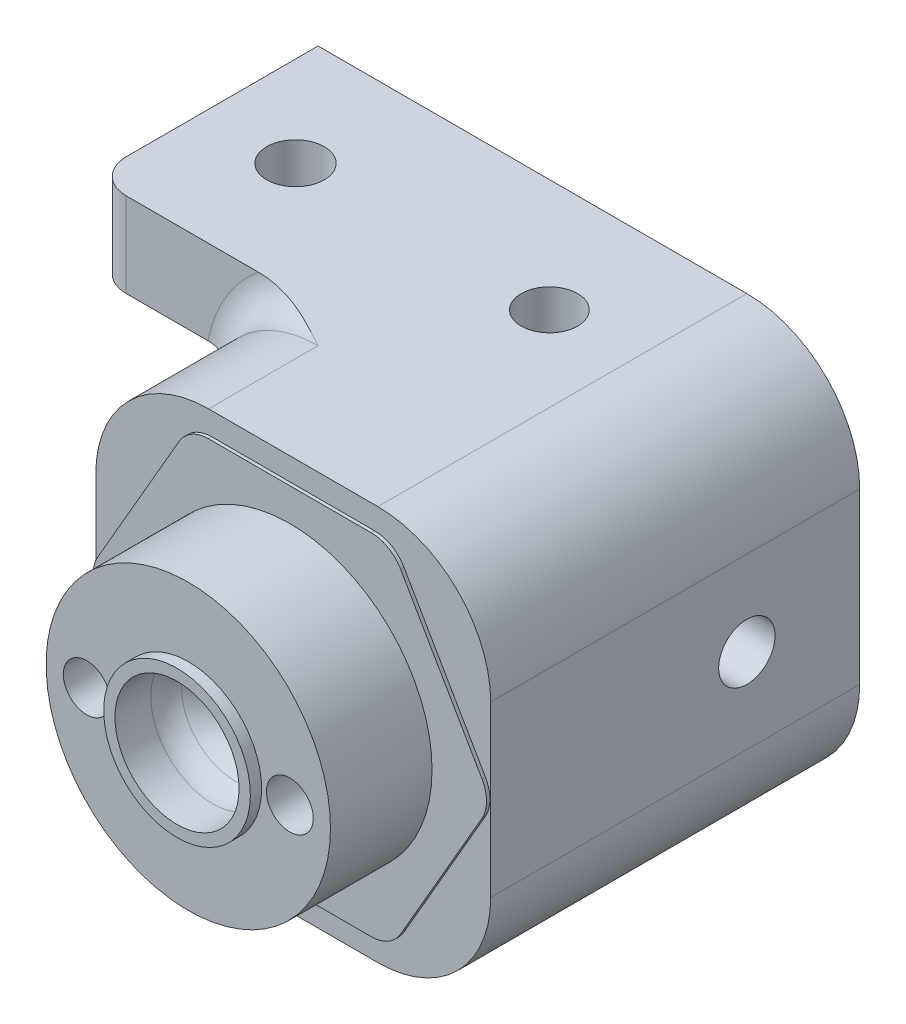
SolidWorks part; units mm, degrees
ref_plane "前视基准面" through (0, 0, 0) normal (0, 0, 1) x (1, 0, 0)
ref_plane "上视基准面" through (0, 0, 0) normal (0, 1, 0) x (1, 0, 0)
ref_plane "右视基准面" through (0, 0, 0) normal (1, 0, 0) x (0, 0, -1)
sketch "草图1" plane through (0, 0, 0) normal (0, 0, 1) x (1, 0, 0)
  circle A0 centre (0, 0) radius 12.6
  dimension "D1" = 25.2
extrude "凸台-拉伸1" add sketch "草图1" along normal blind 9
sketch "草图2" plane through (0, 0, 0) normal (0, 0, -1) x (-1, 0, 0)
  circle A0 centre (0, 0) radius 15
  dimension "D1" = 30
extrude "凸台-拉伸2" add sketch "草图2" along normal blind 5
sketch "草图3" plane through (0, 0, 9) normal (0, 0, 1) x (1, 0, 0)
  circle A0 centre (0, 0) radius 5.5
  dimension "D1" = 11
extrude "切除-拉伸1" cut sketch "草图3" against normal blind 5
sketch "草图4" plane through (0, 0, 9) normal (0, 0, 1) x (1, 0, 0)
  circle A0 centre (-9, 0) radius 2.075
  circle A1 centre (9, 0) radius 2.075
  dimension "D1" = 4.15
  dimension "D2" = 9
  dimension "D3" = 9
extrude "切除-拉伸2" cut sketch "草图4" against normal blind 29
sketch "草图5" plane through (0, 0, 4) normal (0, 0, 1) x (1, 0, 0)
  circle A0 centre (0, 0) radius 3.5
  dimension "D1" = 7
extrude "切除-拉伸3" cut sketch "草图5" against normal blind 31
fillet "圆角1" radius 3 1 edges at (5.5, 0, 4)
fillet "圆角2" radius 5 1 edges at (3.5, 0, 4)
sketch "草图6" plane through (0, 0, 9) normal (0, 0, 1) x (1, 0, 0)
  circle A0 centre (0, 0) radius 5.5
  dimension "D1" = 11
extrude "拉伸-薄壁1" add sketch "草图6" along normal blind 1 thin thin type one direction wall 1
sketch "草图7" plane through (0, 0, -5) normal (0, 0, -1) x (-1, 0, 0)
  line L1 (-8.9489, 15.5) -> (-17.8979, 0)
  line L2 (-17.8979, 0) -> (-8.9489, -15.5)
  line L3 (-8.9489, -15.5) -> (8.9489, -15.5)
  line L4 (8.9489, -15.5) -> (17.8979, 0)
  line L5 (17.8979, 0) -> (8.9489, 15.5)
  line L6 (8.9489, 15.5) -> (-8.9489, 15.5)
  circle A0 centre (0, 0) radius 15.5 construction
  circle A1 centre (0, 0) radius 15
  circle A2 centre (0, 0) radius 15
  dimension "D2" = 31
  dimension "D1" = 0
extrude "凸台-拉伸3" add sketch "草图7" against normal up to surface (5 mm away) up to face at (12.6, 0, 0)
fillet "圆角3" radius 3 6 edges at (17.8979, 0, -2.5) (8.9489, 15.5, -2.5) (-8.9489, 15.5, -2.5) (-17.8979, 0, -2.5) (-8.9489, -15.5, -2.5) (8.9489, -15.5, -2.5)
sketch "草图8" plane through (0, 0, -5) normal (0, 0, -1) x (-1, 0, 0)
  line L6 (-9.815, 14) -> (-17.0318, 1.5)
  line L7 (-17.0318, -1.5) -> (-9.815, -14)
  line L8 (-7.2169, -15.5) -> (7.2169, -15.5)
  line L9 (9.815, -14) -> (17.0318, -1.5)
  line L10 (17.0318, 1.5) -> (9.815, 14)
  line L11 (7.2169, 15.5) -> (-7.2169, 15.5)
  line L12 (-9.815, 14) -> (-17.0318, 1.5)
  line L13 (-17.0318, -1.5) -> (-9.815, -14)
  line L14 (-7.2169, -15.5) -> (7.2169, -15.5)
  line L15 (9.815, -14) -> (17.0318, -1.5)
  line L16 (17.0318, 1.5) -> (9.815, 14)
  line L17 (7.2169, 15.5) -> (-7.2169, 15.5)
  circle A0 centre (0, 0) radius 3.5 construction
  circle A1 centre (0, 0) radius 3.5
  circle A2 centre (-9, 0) radius 4
  circle A3 centre (9, 0) radius 4
  arc A6 (-17.0318, 1.5) -> (-17.0318, -1.5) centre (-14.4338, 0) ccw
  arc A7 (-9.815, -14) -> (-7.2169, -15.5) centre (-7.2169, -12.5) ccw
  arc A8 (7.2169, -15.5) -> (9.815, -14) centre (7.2169, -12.5) ccw
  arc A9 (17.0318, -1.5) -> (17.0318, 1.5) centre (14.4338, 0) ccw
  arc A10 (9.815, 14) -> (7.2169, 15.5) centre (7.2169, 12.5) ccw
  arc A11 (-7.2169, 15.5) -> (-9.815, 14) centre (-7.2169, 12.5) ccw
  arc A12 (-17.0318, 1.5) -> (-17.0318, -1.5) centre (-14.4338, 0) ccw
  arc A13 (-9.815, -14) -> (-7.2169, -15.5) centre (-7.2169, -12.5) ccw
  arc A14 (7.2169, -15.5) -> (9.815, -14) centre (7.2169, -12.5) ccw
  arc A15 (17.0318, -1.5) -> (17.0318, 1.5) centre (14.4338, 0) ccw
  arc A16 (9.815, 14) -> (7.2169, 15.5) centre (7.2169, 12.5) ccw
  arc A17 (-7.2169, 15.5) -> (-9.815, 14) centre (-7.2169, 12.5) ccw
  dimension "D2" = 8
  dimension "D3" = 8
  dimension "D1" = 0
extrude "凸台-拉伸4" add sketch "草图8" along normal blind 8
sketch "草图9" plane through (0, 0, -13) normal (0, 0, -1) x (-1, 0, 0)
  line L1 (-10, 10) -> (10, 10)
  line L2 (-10, 10) -> (-10, -10)
  line L3 (-10, -10) -> (10, -10)
  line L4 (10, 10) -> (10, -10)
  line L5 (-10, 10) -> (10, -10) construction
  line L6 (-10, -10) -> (10, 10) construction
  line L7 (17.5, -17.5) -> (-17.5, -17.5)
  line L8 (17.5, -17.5) -> (17.5, 17.5)
  line L9 (17.5, 17.5) -> (-17.5, 17.5)
  line L10 (-17.5, -17.5) -> (-17.5, 17.5)
  line L11 (17.5, -17.5) -> (-17.5, 17.5) construction
  line L12 (17.5, 17.5) -> (-17.5, -17.5) construction
  point P0 (0, 0)
  point P6 (0, 0)
  dimension "D1" = 20
  dimension "D2" = 20
  dimension "D3" = 35
  dimension "D4" = 35
extrude "凸台-拉伸5" add sketch "草图9" along normal blind 20
sketch "草图10" plane through (0, 0, -13) normal (0, 0, 1) x (1, 0, 0)
  line L4 (17.5, -17.5) -> (17.5, 17.5)
  line L5 (17.5, 17.5) -> (-17.5, 17.5)
  line L6 (-17.5, 17.5) -> (-17.5, -17.5)
  line L7 (-17.5, -17.5) -> (17.5, -17.5)
  line L8 (17.5, -17.5) -> (17.5, 17.5)
  line L9 (17.5, 17.5) -> (-17.5, 17.5)
  line L10 (-17.5, 17.5) -> (-17.5, -17.5)
  line L11 (-17.5, -17.5) -> (17.5, -17.5)
  line L14 (7.2169, 15.5) -> (-7.2169, 15.5)
  line L15 (17.0318, 1.5) -> (9.815, 14)
  line L16 (9.815, -14) -> (17.0318, -1.5)
  line L17 (-7.2169, -15.5) -> (7.2169, -15.5)
  line L18 (-17.0318, -1.5) -> (-9.815, -14)
  line L19 (-9.815, 14) -> (-17.0318, 1.5)
  line L20 (7.2169, 15.5) -> (-7.2169, 15.5)
  line L21 (17.0318, 1.5) -> (9.815, 14)
  line L22 (9.815, -14) -> (17.0318, -1.5)
  line L23 (-7.2169, -15.5) -> (7.2169, -15.5)
  line L24 (-17.0318, -1.5) -> (-9.815, -14)
  line L25 (-9.815, 14) -> (-17.0318, 1.5)
  arc A6 (9.815, 14) -> (7.2169, 15.5) centre (7.2169, 12.5) ccw
  arc A7 (17.0318, -1.5) -> (17.0318, 1.5) centre (14.4338, 0) ccw
  arc A8 (7.2169, -15.5) -> (9.815, -14) centre (7.2169, -12.5) ccw
  arc A9 (-9.815, -14) -> (-7.2169, -15.5) centre (-7.2169, -12.5) ccw
  arc A10 (-17.0318, 1.5) -> (-17.0318, -1.5) centre (-14.4338, 0) ccw
  arc A11 (-7.2169, 15.5) -> (-9.815, 14) centre (-7.2169, 12.5) ccw
  arc A12 (9.815, 14) -> (7.2169, 15.5) centre (7.2169, 12.5) ccw
  arc A13 (17.0318, -1.5) -> (17.0318, 1.5) centre (14.4338, 0) ccw
  arc A14 (7.2169, -15.5) -> (9.815, -14) centre (7.2169, -12.5) ccw
  arc A15 (-9.815, -14) -> (-7.2169, -15.5) centre (-7.2169, -12.5) ccw
  arc A16 (-17.0318, 1.5) -> (-17.0318, -1.5) centre (-14.4338, 0) ccw
  arc A17 (-7.2169, 15.5) -> (-9.815, 14) centre (-7.2169, 12.5) ccw
  dimension "D1" = 0
  dimension "D2" = 0
extrude "凸台-拉伸6" add sketch "草图10" along normal blind 8.5
fillet "圆角4" radius 10 4 edges at (-17.5, 17.5, -18.75) (-17.5, -17.5, -18.75) (17.5, -17.5, -18.75) (17.5, 17.5, -18.75)
sketch "草图11" plane through (-17.5, 0, 0) normal (-1, 0, 0) x (0, 0, 1)
  line L0 (-33, -7.5) -> (-33, 7.5) construction
  circle A0 centre (-23, 0) radius 2.5
  dimension "D1" = 5
  dimension "D2" = 10
extrude "切除-拉伸4" cut sketch "草图11" against normal blind 15
pattern_circular "阵列(圆周)1" count 4 over 360 about axis through (0, 0, -27) along (0, 0, 1) of "切除-拉伸4"
sketch "草图12" plane through (0, 0, -5) normal (0, 0, -1) x (-1, 0, 0)
  circle A1 centre (9, 0) radius 4
  circle A2 centre (9, 0) radius 4
  circle A3 centre (-9, 0) radius 4
  circle A4 centre (-9, 0) radius 4
  dimension "D1" = 0
  dimension "D2" = 0
extrude "切除-拉伸5" cut sketch "草图12" along normal blind 83
sketch "草图13" plane through (0, 0, -13) normal (0, 0, -1) x (-1, 0, 0)
  line L0 (0, 3.5) -> (0, 10)
  line L1 (10, 10) -> (-10, 10) construction
  line L2 (0, 0) -> (0, 3.5)
  circle A0 centre (0, 0) radius 3.5 construction
extrude "切除-拉伸-薄壁1" [suppressed] cut sketch "草图13" against normal blind 4 thin thin type mid plane wall 4
fillet "圆角5" [suppressed] radius 4
fillet "圆角6" [suppressed] radius 4
fillet "圆角7" [suppressed] radius 3
sketch "草图14" plane through (0, 0, -13) normal (0, 0, -1) x (-1, 0, 0)
  line L0 (-10, -10) -> (10, -10) construction
  line L1 (10, 10) -> (33.2128, 10)
  line L2 (10, 10) -> (10, -10)
  line L3 (10, -10) -> (33.2128, -10)
  line L4 (33.2128, 10) -> (33.2128, -10)
extrude "切除-拉伸6" cut sketch "草图14" along normal blind 41
sketch "草图15" plane through (0, 0, -4.5) normal (0, 0, 1) x (1, 0, 0)
  line L4 (7.5, 17.5) -> (-7.5, 17.5)
  line L5 (-17.5, 7.5) -> (-17.5, -7.5)
  line L6 (-7.5, -17.5) -> (7.5, -17.5)
  line L7 (17.5, -7.5) -> (17.5, 7.5)
  line L8 (7.5, 17.5) -> (-7.5, 17.5)
  line L9 (-17.5, 7.5) -> (-17.5, -7.5)
  line L10 (-7.5, -17.5) -> (7.5, -17.5)
  line L11 (17.5, -7.5) -> (17.5, 7.5)
  line L14 (9.815, -14) -> (17.0318, -1.5)
  line L15 (17.0318, 1.5) -> (9.815, 14)
  line L16 (7.2169, 15.5) -> (-7.2169, 15.5)
  line L17 (-9.815, 14) -> (-17.0318, 1.5)
  line L18 (-17.0318, -1.5) -> (-9.815, -14)
  line L19 (-7.2169, -15.5) -> (7.2169, -15.5)
  line L20 (9.815, -14) -> (17.0318, -1.5)
  line L21 (17.0318, 1.5) -> (9.815, 14)
  line L22 (7.2169, 15.5) -> (-7.2169, 15.5)
  line L23 (-9.815, 14) -> (-17.0318, 1.5)
  line L24 (-17.0318, -1.5) -> (-9.815, -14)
  line L25 (-7.2169, -15.5) -> (7.2169, -15.5)
  arc A4 (-7.5, 17.5) -> (-17.5, 7.5) centre (-7.5, 7.5) ccw
  arc A5 (-17.5, -7.5) -> (-7.5, -17.5) centre (-7.5, -7.5) ccw
  arc A6 (7.5, -17.5) -> (17.5, -7.5) centre (7.5, -7.5) ccw
  arc A7 (17.5, 7.5) -> (7.5, 17.5) centre (7.5, 7.5) ccw
  arc A8 (-7.5, 17.5) -> (-17.5, 7.5) centre (-7.5, 7.5) ccw
  arc A9 (-17.5, -7.5) -> (-7.5, -17.5) centre (-7.5, -7.5) ccw
  arc A10 (7.5, -17.5) -> (17.5, -7.5) centre (7.5, -7.5) ccw
  arc A11 (17.5, 7.5) -> (7.5, 17.5) centre (7.5, 7.5) ccw
  arc A14 (17.0318, -1.5) -> (17.0318, 1.5) centre (14.4338, 0) ccw
  arc A15 (9.815, 14) -> (7.2169, 15.5) centre (7.2169, 12.5) ccw
  arc A16 (-7.2169, 15.5) -> (-9.815, 14) centre (-7.2169, 12.5) ccw
  arc A17 (-17.0318, 1.5) -> (-17.0318, -1.5) centre (-14.4338, 0) ccw
  arc A18 (-9.815, -14) -> (-7.2169, -15.5) centre (-7.2169, -12.5) ccw
  arc A19 (7.2169, -15.5) -> (9.815, -14) centre (7.2169, -12.5) ccw
  arc A20 (17.0318, -1.5) -> (17.0318, 1.5) centre (14.4338, 0) ccw
  arc A21 (9.815, 14) -> (7.2169, 15.5) centre (7.2169, 12.5) ccw
  arc A22 (-7.2169, 15.5) -> (-9.815, 14) centre (-7.2169, 12.5) ccw
  arc A23 (-17.0318, 1.5) -> (-17.0318, -1.5) centre (-14.4338, 0) ccw
  arc A24 (-9.815, -14) -> (-7.2169, -15.5) centre (-7.2169, -12.5) ccw
  arc A25 (7.2169, -15.5) -> (9.815, -14) centre (7.2169, -12.5) ccw
  dimension "D1" = 0
  dimension "D2" = 0
extrude "凸台-拉伸7" add sketch "草图15" along normal blind 1.3
sketch "草图16" plane through (0, 0, -13) normal (0, 0, -1) x (-1, 0, 0)
  line L1 (0, 3.5) -> (-9.9868, 3.5)
  line L2 (0, 3.5) -> (0, -3.5)
  line L3 (0, -3.5) -> (-9.9868, -3.5)
  line L4 (-9.9868, 3.5) -> (-9.9868, -3.5)
  circle A0 centre (0, 0) radius 3.5 construction
  dimension "D1" = 7
extrude "切除-拉伸7" cut sketch "草图16" against normal blind 3
sketch "草图18" plane through (0, 0, -13) normal (0, 0, -1) x (-1, 0, 0)
  line L0 (17.1825, 10) -> (-10, 10) construction
  line L1 (7.5, 17.5) -> (30.5, 17.5)
  line L2 (7.5, 17.5) -> (7.5, 10)
  line L3 (7.5, 10) -> (30.5, 10)
  line L4 (30.5, 17.5) -> (30.5, 10)
  dimension "D1" = 7.5
  dimension "D2" = 23
extrude "凸台-拉伸8" add sketch "草图18" along normal blind 20
sketch "草图19" plane through (0, 17.5, 0) normal (0, 1, 0) x (1, 0, 0)
  line L0 (-30.5, 33) -> (7.5, 33) construction
  line L1 (-30.5, 33) -> (-30.5, 13) construction
  circle A0 centre (-22.5, 23) radius 2.55
  dimension "D1" = 5.1
  dimension "D2" = 10
  dimension "D3" = 8
extrude "切除-拉伸8" cut sketch "草图19" against normal blind 20
mirror "镜向1" about plane through (0, 0, 0) normal (0, 1, 0) of "切除-拉伸8", "凸台-拉伸8"
fillet "圆角8" radius 3 2 edges at (-13.6237, 15.4057, -13) (-13.6237, -15.4057, -13)
fillet "圆角9" radius 3 2 edges at (-30.5, 13.75, -13) (-30.5, -13.75, -13)
sketch "草图20" plane through (0, 0, -3.2) normal (0, 0, 1) x (1, 0, 0)
  line L4 (7.5, 17.5) -> (-7.5, 17.5)
  line L5 (-17.5, 7.5) -> (-17.5, -7.5)
  line L6 (-7.5, -17.5) -> (7.5, -17.5)
  line L7 (17.5, -7.5) -> (17.5, 7.5)
  line L8 (7.5, 17.5) -> (-7.5, 17.5)
  line L9 (-17.5, 7.5) -> (-17.5, -7.5)
  line L10 (-7.5, -17.5) -> (7.5, -17.5)
  line L11 (17.5, -7.5) -> (17.5, 7.5)
  line L14 (9.815, -14) -> (17.0318, -1.5)
  line L15 (17.0318, 1.5) -> (9.815, 14)
  line L16 (7.2169, 15.5) -> (-7.2169, 15.5)
  line L17 (-9.815, 14) -> (-17.0318, 1.5)
  line L18 (-17.0318, -1.5) -> (-9.815, -14)
  line L19 (-7.2169, -15.5) -> (7.2169, -15.5)
  line L20 (9.815, -14) -> (17.0318, -1.5)
  line L21 (17.0318, 1.5) -> (9.815, 14)
  line L22 (7.2169, 15.5) -> (-7.2169, 15.5)
  line L23 (-9.815, 14) -> (-17.0318, 1.5)
  line L24 (-17.0318, -1.5) -> (-9.815, -14)
  line L25 (-7.2169, -15.5) -> (7.2169, -15.5)
  arc A4 (17.5, 7.5) -> (7.5, 17.5) centre (7.5, 7.5) ccw
  arc A5 (-7.5, 17.5) -> (-17.5, 7.5) centre (-7.5, 7.5) ccw
  arc A6 (-17.5, -7.5) -> (-7.5, -17.5) centre (-7.5, -7.5) ccw
  arc A7 (7.5, -17.5) -> (17.5, -7.5) centre (7.5, -7.5) ccw
  arc A8 (17.5, 7.5) -> (7.5, 17.5) centre (7.5, 7.5) ccw
  arc A9 (-7.5, 17.5) -> (-17.5, 7.5) centre (-7.5, 7.5) ccw
  arc A10 (-17.5, -7.5) -> (-7.5, -17.5) centre (-7.5, -7.5) ccw
  arc A11 (7.5, -17.5) -> (17.5, -7.5) centre (7.5, -7.5) ccw
  arc A14 (17.0318, -1.5) -> (17.0318, 1.5) centre (14.4338, 0) ccw
  arc A15 (9.815, 14) -> (7.2169, 15.5) centre (7.2169, 12.5) ccw
  arc A16 (-7.2169, 15.5) -> (-9.815, 14) centre (-7.2169, 12.5) ccw
  arc A17 (-17.0318, 1.5) -> (-17.0318, -1.5) centre (-14.4338, 0) ccw
  arc A18 (-9.815, -14) -> (-7.2169, -15.5) centre (-7.2169, -12.5) ccw
  arc A19 (7.2169, -15.5) -> (9.815, -14) centre (7.2169, -12.5) ccw
  arc A20 (17.0318, -1.5) -> (17.0318, 1.5) centre (14.4338, 0) ccw
  arc A21 (9.815, 14) -> (7.2169, 15.5) centre (7.2169, 12.5) ccw
  arc A22 (-7.2169, 15.5) -> (-9.815, 14) centre (-7.2169, 12.5) ccw
  arc A23 (-17.0318, 1.5) -> (-17.0318, -1.5) centre (-14.4338, 0) ccw
  arc A24 (-9.815, -14) -> (-7.2169, -15.5) centre (-7.2169, -12.5) ccw
  arc A25 (7.2169, -15.5) -> (9.815, -14) centre (7.2169, -12.5) ccw
  dimension "D1" = 0
  dimension "D2" = 0
extrude "凸台-拉伸9" add sketch "草图20" along normal offset from surface (2.9 mm away) 0.3 up to face at (12.6, 0, 0)
